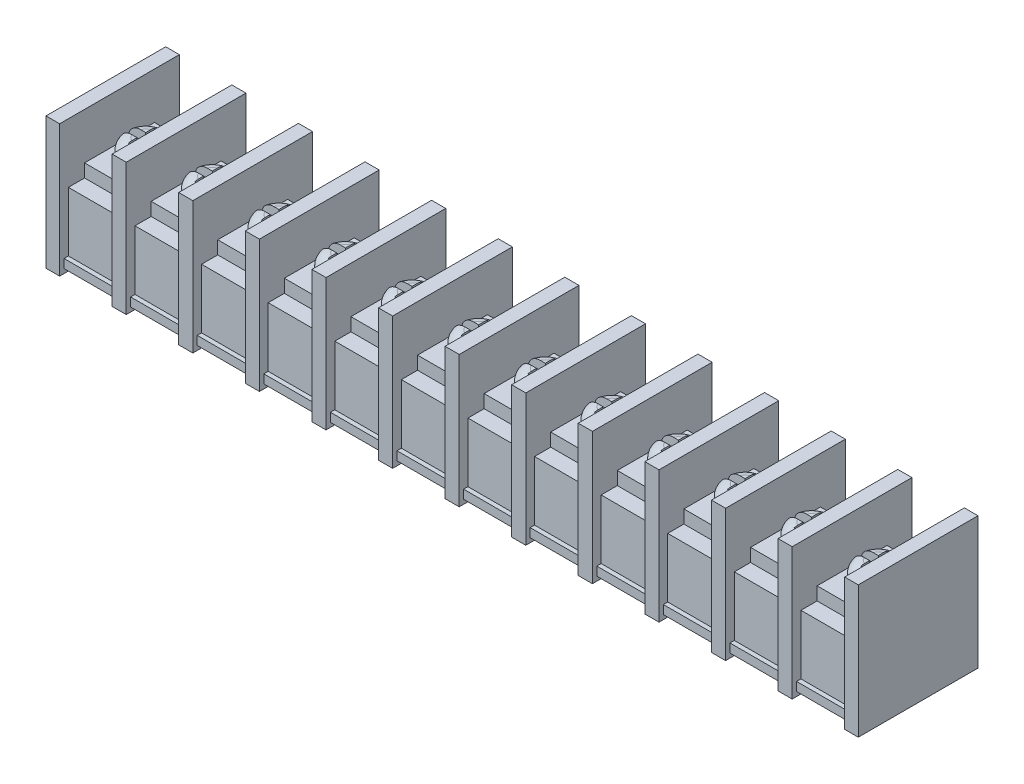
SolidWorks part; units mm, degrees
ref_plane "前视基准面" through (0, 0, 0) normal (0, 0, 1) x (1, 0, 0)
ref_plane "上视基准面" through (0, 0, 0) normal (0, 1, 0) x (1, 0, 0)
ref_plane "右视基准面" through (0, 0, 0) normal (1, 0, 0) x (0, 0, -1)
sketch "草图2" plane through (0, 0, 0) normal (0, 0, 1) x (1, 0, 0)
  line L0 (0, 0) -> (0, 12.5432) construction
  line L1 (-3.81, 0) -> (3.81, 0)
  line L2 (-3.81, 0) -> (-3.81, 15.1)
  line L3 (-3.81, 15.1) -> (-3, 15.1)
  line L4 (3.81, 0) -> (3.81, 15.1)
  line L5 (-3, 8.3) -> (3, 8.3)
  line L6 (-3, 8.3) -> (-3, 15.1)
  line L7 (3, 15.1) -> (3.81, 15.1)
  line L8 (3, 8.3) -> (3, 15.1)
  point P5 (0, 11.7)
  dimension "D1" = 7.62
  dimension "D2" = 15.1
  dimension "D3" = 8.3
  dimension "D4" = 6
  dimension "D5" = 0.81
extrude "凸台-拉伸1" add sketch "草图2" along normal mid plane 13.7
sketch "草图3" plane through (0, 8.3, 0) normal (0, 1, 0) x (1, 0, 0)
  line L0 (3, -6.85) -> (3, 6.85) construction
  line L1 (-3, 6.85) -> (3, 6.85)
  line L2 (-3, 6.85) -> (-3, 5.85)
  line L3 (-3, 5.85) -> (3, 5.85)
  line L4 (3, 6.85) -> (3, 5.85)
  line L5 (-3.81, 0) -> (10.4109, 0) construction
  line L6 (-3, -6.85) -> (3, -6.85)
  line L7 (-3, -6.85) -> (-3, -5.85)
  line L8 (-3, -5.85) -> (3, -5.85)
  line L9 (3, -6.85) -> (3, -5.85)
  line L10 (-3.81, -6.85) -> (-3.81, 6.85) construction
  dimension "D1" = 1
extrude "切除-拉伸1" cut sketch "草图3" against normal offset from surface (6.8 mm away) 1.5 up to face at (0, 0, 0)
sketch "草图4" plane through (0, 0, -6.85) normal (0, 0, -1) x (-1, 0, 0)
  line L0 (3.81, 0) -> (-3.81, 0) construction
  line L1 (3, 0) -> (-3, 0)
  line L2 (3, 0) -> (3, 0.5)
  line L3 (3, 0.5) -> (-3, 0.5)
  line L4 (-3, 0) -> (-3, 0.5)
  line L5 (3, 1.5) -> (3, 8.3) construction
  line L6 (-3, 1.5) -> (-3, 8.3) construction
  dimension "D1" = 0.5
extrude "切除-拉伸2" cut sketch "草图4" against normal through all
sketch "草图5" plane through (0, 0.5, 0) normal (0, -1, 0) x (1, 0, 0)
  line L0 (-3, 6.85) -> (-3, -6.85) construction
  line L1 (3, -6.85) -> (-3, -6.85)
  line L2 (3, -6.85) -> (3, -6.35)
  line L3 (3, -6.35) -> (-3, -6.35)
  line L4 (-3, -6.85) -> (-3, -6.35)
  line L5 (-3, 6.85) -> (-3, -6.85) construction
  line L6 (3, 6.85) -> (-3, 6.85)
  line L7 (3, 6.85) -> (3, 6.35)
  line L8 (3, 6.35) -> (-3, 6.35)
  line L9 (-3, 6.85) -> (-3, 6.35)
  line L10 (3.81, 0) -> (-1.2087, 0) construction
  line L11 (3.81, 6.85) -> (3.81, -6.85) construction
  dimension "D1" = 0.5
extrude "切除-拉伸3" cut sketch "草图5" against normal through all
sketch "草图8" plane through (0, 8.3, 0) normal (0, 1, 0) x (1, 0, 0)
  line L1 (3, -5.85) -> (3, 5.85) construction
  line L2 (-3, -4) -> (3, -4)
  line L3 (-3, -4) -> (-3, 4)
  line L4 (-3, 4) -> (3, 4)
  line L6 (3, -4) -> (3, 4)
  line L7 (-3, -4) -> (3, 4) construction
  line L8 (-3, 4) -> (3, -4) construction
  point P0 (0, 0)
  dimension "D1" = 8
extrude "凸台-拉伸4" add sketch "草图8" along normal blind 1.5
sketch "草图9" plane through (0, 0, 0) normal (0, 0, 1) x (1, 0, 0)
  line L0 (2.2954, 9.8) -> (0, 9.8)
  line L1 (-3, 9.8) -> (3, 9.8) construction
  line L2 (0, 9.8) -> (0, 11.8)
  line L3 (0, 11.8) -> (1.2, 11.8)
  arc A0 (1.2, 11.8) -> (2.2954, 9.8) centre (1.2, 10.5) cw
  dimension "D2" = 2.5
  dimension "D1" = 2
  dimension "D3" = 1.2
revolve "旋转1" add sketch "草图9" angle 360 about L2
sketch "草图10" plane through (0, 11.8, 0) normal (0, 1, 0) x (1, 0, 0)
  line L0 (-2.75, 0) -> (2.75, 0) construction
  line L1 (0, 1.5) -> (0, -1.5) construction
  line L2 (-2.75, -0.5) -> (-0.5, -0.5)
  line L3 (-2.75, 0.5) -> (-0.5, 0.5)
  line L4 (-0.5, 1.5) -> (-0.5, 0.5)
  line L5 (0.5, 1.5) -> (0.5, 0.5)
  line L6 (-2.75, -0.5) -> (-2.75, 0.5)
  line L7 (2.75, 0.5) -> (2.75, -0.5)
  line L8 (-0.5, 1.5) -> (0.5, 1.5)
  line L9 (-0.5, -1.5) -> (0.5, -1.5)
  line L10 (0.5, 0.5) -> (2.75, 0.5)
  line L11 (-2.75, 0.5) -> (2.75, 0.5) construction
  line L12 (-0.5, -0.5) -> (-0.5, -1.5)
  line L13 (-0.5, 1.5) -> (-0.5, -1.5) construction
  line L14 (0.5, -0.5) -> (0.5, -1.5)
  line L15 (0.5, 1.5) -> (0.5, -1.5) construction
  line L16 (0.5, -0.5) -> (2.75, -0.5)
  line L17 (-2.75, -0.5) -> (2.75, -0.5) construction
  point P5 (0, 0)
  point P9 (0, 0)
  dimension "D5" = 3
  dimension "D6" = 5.5
  dimension "D1" = 0.5
  dimension "D2" = 0.5
  dimension "D3" = 0.5
  dimension "D4" = 0.5
extrude "切除-拉伸4" cut sketch "草图10" against normal blind 1
sketch "草图11" plane through (0, 0.5, 0) normal (0, -1, 0) x (1, 0, 0)
  line L1 (-0.6, -0.4) -> (0.6, -0.4)
  line L2 (-0.6, -0.4) -> (-0.6, 0.4)
  line L3 (-0.6, 0.4) -> (0.6, 0.4)
  line L4 (0.6, -0.4) -> (0.6, 0.4)
  line L5 (-0.6, -0.4) -> (0.6, 0.4) construction
  line L6 (-0.6, 0.4) -> (0.6, -0.4) construction
  point P0 (0, 0)
  dimension "D1" = 1.2
  dimension "D2" = 0.8
extrude "凸台-拉伸5" add sketch "草图11" along normal blind 4.2
ref_plane "左" through (-3.81, 0, 0) normal (1, 0, 0) x (0, 0, -1)
pattern_linear "个数" count 12 spacing 7.62 along (1, 0, 0) of "凸台-拉伸1", "切除-拉伸1", "切除-拉伸3", "切除-拉伸2", "凸台-拉伸4", "凸台-拉伸5", "切除-拉伸4", "旋转1"
ref_plane "7.62*N" through (87.63, 0, 0) normal (1, 0, 0) x (0, 0, -1)
sketch "草图7" plane through (-3.81, 0, 0) normal (1, 0, 0) x (0, 0, -1)
  line L0 (-6.85, 15.1) -> (-6.85, 0) construction
  line L1 (-6.85, 0) -> (6.85, 0) construction
  line L2 (6.85, 15.1) -> (6.85, 0) construction
  line L3 (-6.85, 15.1) -> (6.85, 15.1) construction
  line L4 (-6.85, 15.1) -> (-6.85, 0)
  line L5 (-6.85, 0) -> (6.85, 0)
  line L6 (6.85, 15.1) -> (6.85, 0)
  line L7 (-6.85, 15.1) -> (6.85, 15.1)
extrude "左0.75 " add sketch "草图7" against normal blind 0.75
sketch "草图6" plane through (87.63, 0, 0) normal (-1, 0, 0) x (0, 0, 1)
  line L5 (6.85, 0) -> (-6.85, 0)
  line L6 (6.85, 0) -> (6.85, 15.1)
  line L7 (6.85, 15.1) -> (-6.85, 15.1)
  line L8 (-6.85, 0) -> (-6.85, 15.1)
  point P4 (0, 0)
  dimension "D1" = 13.7
  dimension "D2" = 15.1
extrude "右0.75" add sketch "草图6" against normal blind 0.75
equation "\"D1@7.62*N\"   = 7.62 * \"D1@个数\""
